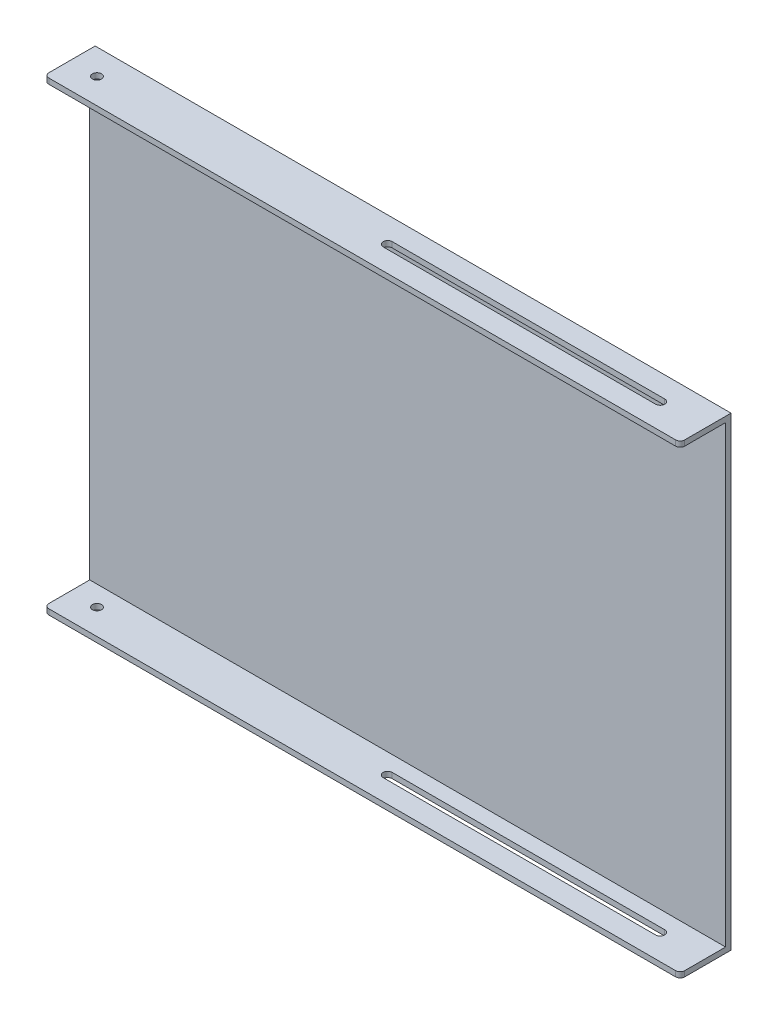
SolidWorks part; units mm, degrees
ref_plane "Front Plane" through (0, 0, 0) normal (0, 0, 1) x (1, 0, 0)
ref_plane "Top Plane" through (0, 0, 0) normal (0, 1, 0) x (1, 0, 0)
ref_plane "Right Plane" through (0, 0, 0) normal (1, 0, 0) x (0, 0, -1)
sketch "Sketch4" plane through (0, 0, 0) normal (0, 1, 0) x (1, 0, 0)
  line L0 (0, 0) -> (300, 0) construction
  line L1 (-350, 28) -> (350, 28)
  line L2 (-350, 28) -> (-350, -23)
  line L3 (-345, -28) -> (345, -28)
  line L4 (350, 28) -> (350, -23)
  line L5 (0, 5) -> (300, 5)
  line L6 (0, -5) -> (300, -5)
  arc A0 (0, 5) -> (0, -5) centre (0, 0) ccw
  arc A1 (300, -5) -> (300, 5) centre (300, 0) ccw
  circle A2 centre (-320, 0) radius 5
  arc A3 (345, -28) -> (350, -23) centre (345, -23) ccw
  arc A4 (-345, -28) -> (-350, -23) centre (-345, -23) cw
  point P0 (0, 0)
  point P8 (150, 0)
  dimension "D7" = 10
  dimension "D10" = 5
  dimension "D1" = 350
  dimension "D2" = 28
  dimension "D3" = 350
  dimension "D4" = 28
  dimension "D5" = 300
  dimension "D6" = 5
  dimension "D8" = 30
  dimension "D9" = 28
extrude "Boss-Extrude2" add sketch "Sketch4" along normal mid plane 512
sketch "Sketch5" plane through (350, 0, 0) normal (1, 0, 0) x (0, 0, -1)
  line L0 (-28, 256) -> (-28, -256) construction
  line L1 (-28, 250) -> (-28, -250)
  line L12 (-28, -250) -> (22, -250)
  line L13 (22, -250) -> (22, 250)
  line L14 (22, 250) -> (-28, 250)
extrude "Cut-Extrude2" cut sketch "Sketch5" against normal through all both and the other way through all
